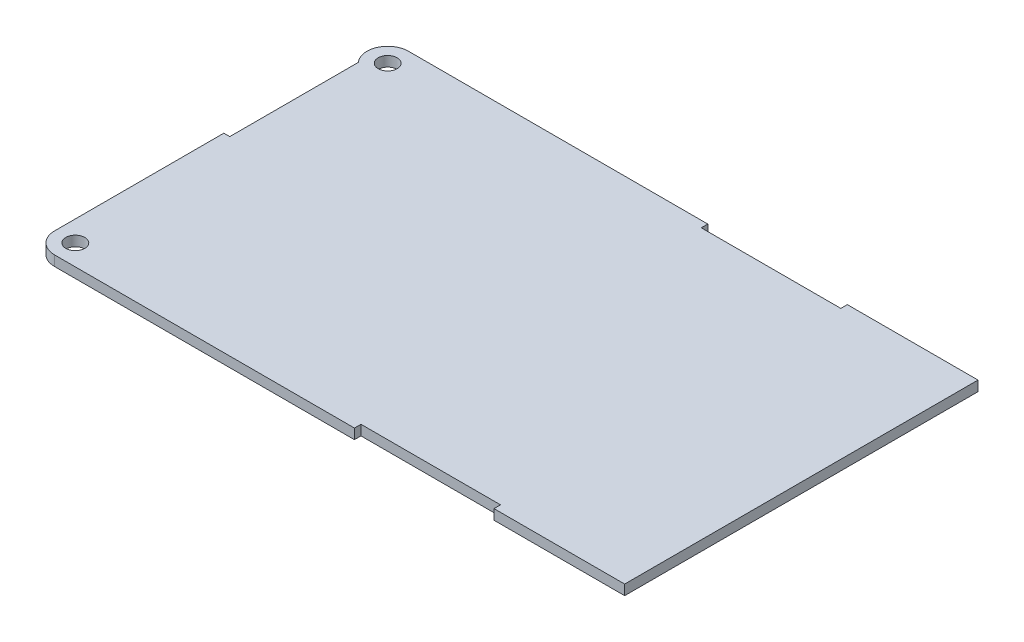
SolidWorks part; units mm, degrees
ref_plane "Front Plane" through (0, 0, 0) normal (0, 0, 1) x (1, 0, 0)
ref_plane "Top Plane" through (0, 0, 0) normal (0, 1, 0) x (1, 0, 0)
ref_plane "Right Plane" through (0, 0, 0) normal (1, 0, 0) x (0, 0, -1)
sketch "Sketch1" plane through (0, 0, 0) normal (0, 1, 0) x (1, 0, 0)
  line L0 (77.5, 59.5) -> (77.5, 0) construction
  line L1 (3.5, 0) -> (54, 0)
  line L2 (0, 3.5) -> (0, 32)
  line L3 (3.5, 59.5) -> (54, 59.5)
  line L4 (99.5, 0) -> (99.5, 59.5)
  line L5 (54, 59.5) -> (54, 0) construction
  line L6 (77.5, 58.4) -> (54, 58.4) construction
  line L7 (77.5, 1.1) -> (54, 1.1) construction
  line L8 (54, 0) -> (54, 1.1)
  line L9 (54, 1.1) -> (77.5, 1.1)
  line L10 (77.5, 1.1) -> (77.5, 0)
  line L11 (77.5, 0) -> (99.5, 0)
  line L12 (77.5, 59.5) -> (77.5, 58.4)
  line L13 (77.5, 58.4) -> (54, 58.4)
  line L14 (54, 58.4) -> (54, 59.5)
  line L15 (77.5, 59.5) -> (99.5, 59.5)
  line L16 (-8.5176, 32) -> (1, 32) construction
  line L17 (1, 61.8165) -> (1, 32) construction
  line L18 (1, 53.6569) -> (1, 32)
  line L19 (1, 32) -> (0, 32)
  arc A0 (3.5, 0) -> (0, 3.5) centre (3.5, 3.5) cw
  circle A2 centre (3.6, 56) radius 1.6
  circle A3 centre (3.5, 3.5) radius 1.6
  arc A4 (3.6, 59.5) -> (1, 53.6569) centre (3.6, 56) ccw
  point P15 (0, 0)
  point P18 (0, 59.5)
  dimension "D7" = 3.5
  dimension "D8" = 3.5
  dimension "D10" = 3.2
  dimension "D11" = 3.2
  dimension "D15" = 1
  dimension "D9" = 2.6
  dimension "D1" = 59.5
  dimension "D2" = 22
  dimension "D3" = 23.5
  dimension "D4" = 99.5
  dimension "D5" = 1.1
  dimension "D6" = 1.1
  dimension "D14" = 27.5
extrude "Boss-Extrude1" add sketch "Sketch1" along normal blind 1.7 contours L3 A4 L18 L19 L2 A0 L1 L8 L9 L10 L11 L4 L15 L12 L13 L14 A2 A3 region at (49.9735, 0, -29.6959)
